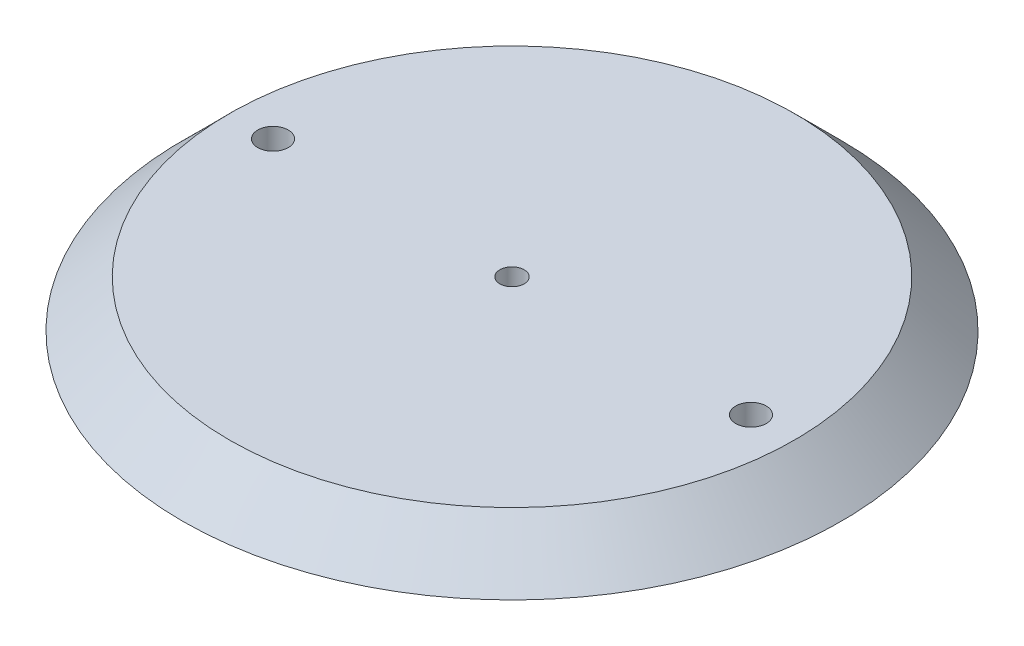
SolidWorks part; units mm, degrees
material "Malleable Cast Iron"
ref_plane "Front Plane" through (0, 0, 0) normal (0, 0, 1) x (1, 0, 0)
ref_plane "Top Plane" through (0, 0, 0) normal (0, 1, 0) x (1, 0, 0)
ref_plane "Right Plane" through (0, 0, 0) normal (1, 0, 0) x (0, 0, -1)
sketch "Sketch1" plane through (0, 0, 0) normal (0, 1, 0) x (1, 0, 0)
  circle A0 centre (0, 0) radius 85.725
  dimension "D1" = 171.45
extrude "Boss-Extrude1" add sketch "Sketch1" along normal blind 12.192 draft 45
hole_wizard "3/8-16 Tapped Hole1" positions "Sketch6" profile "Sketch7" tap size "3/8-16" standard "ANSI Inch" end condition through all
sketch "Sketch6" plane through (0, 12.192, 0) normal (0, 1, 0) x (-0.9997, 0, -0.0242)
  line L2 (54.3263, -144.7753) -> (48.6295, 90.1056) construction
  line L3 (-47.2438, -147.2388) -> (-52.9406, 87.6421) construction
  line L4 (-73.5114, -1.7829) -> (-50.7851, -1.2317) construction
  line L5 (50.7851, 1.2317) -> (73.5114, 1.7829) construction
  line L6 (-50.7851, -1.2317) -> (0, 0) construction
  circle A1 centre (0, 0) radius 73.533 construction
  point P0 (-62.1482, -1.5073)
  point P1 (62.1482, 1.5073)
sketch "Sketch7" plane through (62.1665, 12.192, 0) normal (1, 0, 0) x (0, 0, 1)
  line L0 (0, 0) -> (0, 12.192)
  line L1 (0, 12.192) -> (3.9687, 12.192)
  line L2 (3.9687, 12.192) -> (3.9687, 0)
  line L5 (3.9687, 0) -> (0, 0)
  line L11 (0, -6.35) -> (0, 107.95) construction
  dimension "Thru Tap Drill Dia." = 7.9375
  dimension "Thru Tap Drill Depth" = 12.192
cosmetic thread "Hole Thread1" parameters "D1"=0, "D2"=8.9375
cosmetic thread "Hole Thread2" parameters "D1"=0, "D2"=8.9375
hole_wizard "1/4 (0.25) Press Dowel Hole1" positions "Sketch8" profile "Sketch9" hole size "1/4" standard "ANSI Inch" end condition through all
sketch "Sketch8" plane through (-177.9915, 12.192, 193.466) normal (0, 1, 0) x (-0.9096, 0, -0.4155)
  point P0 (-81.5106, -249.9322)
sketch "Sketch9" plane through (0, 12.192, 0) normal (1, 0, 0) x (0, 0, 1)
  line L0 (0, 0) -> (0, 12.192)
  line L1 (0, 12.192) -> (3.175, 12.192)
  line L2 (3.175, 12.192) -> (3.175, 0)
  line L3 (3.175, 0) -> (0, 0)
  line L4 (0, -6.35) -> (0, 107.95) construction
  dimension "Thru Hole Dia." = 6.35
  dimension "Thru Hole Depth" = 12.192
equation "\"delta-z\" = 1.5"
equation "\"total-height\" = 3.28"
equation "\"mid-height\" = 1.5"
equation "\"jaw-width\" = 4"
equation "\"jaw-height\" = \"total-height\" - \"mid-height\""
equation "\"max-tube-diam\" = 3.5"
equation "\"v-block-notch-height\" = 1.5"
equation "\"v-block-notch-angle\" = 120"
equation "\"vise-mod-plate-thickness\"= .375"
equation "\"vise-mod-height\"= .5 * \"max-tube-diam\" + \"delta-z\""
equation "\"jaw-travel\" = 4.45"
equation "\"rib-top-width\" = 0.5"
equation "\"rib-side-width\" = 0.5"
equation "\"quarter-twenty-close-clearance\" = .257"
equation "\"box-way-width\" = 1.5"
equation "\"box-way-depth\" = 1.5"
equation "\"screw-OD\" = .625"
equation "\"screw-reduced-diam\" = .47"
equation "\"pressure-plate-OD\" = 6.75"
equation "\"D1@Sketch1\"=\"pressure-plate-OD\""
equation "\"swivel-cleat-thick\" = .5"
equation "\"swivel-gap\" = .02"
equation "\"D1@Boss-Extrude1\"=\"swivel-cleat-thick\" - \"swivel-gap\""
